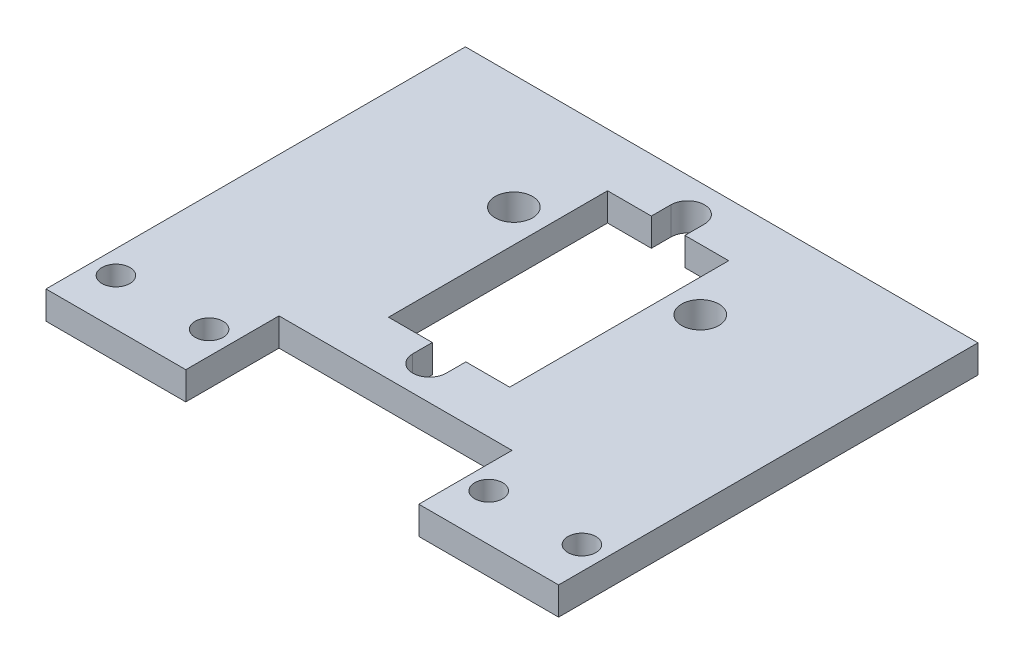
SolidWorks part; units mm, degrees
ref_plane "Front Plane" through (0, 0, 0) normal (0, 0, 1) x (1, 0, 0)
ref_plane "Top Plane" through (0, 0, 0) normal (0, 1, 0) x (1, 0, 0)
ref_plane "Right Plane" through (0, 0, 0) normal (1, 0, 0) x (0, 0, -1)
sketch "Sketch1" plane through (0, 0, 0) normal (0, 1, 0) x (1, 0, 0)
  line L0 (0, 0) -> (15, 0)
  line L1 (15, 0) -> (15, 10)
  line L2 (15, 10) -> (40, 10)
  line L3 (40, 10) -> (40, 0)
  line L4 (40, 0) -> (55, 0)
  line L5 (55, 0) -> (55, 45)
  line L6 (55, 45) -> (0, 45)
  line L7 (0, 45) -> (0, 0)
  line L8 (27.5, 10) -> (27.5, 45) construction
  line L9 (21, 39.25) -> (34, 39.25)
  line L10 (21, 39.25) -> (21, 15.75)
  line L11 (21, 15.75) -> (34, 15.75)
  line L12 (34, 39.25) -> (34, 15.75)
  line L13 (0, 27.5) -> (55, 27.5) construction
  line L14 (27.5, 5) -> (32.5, 5) construction
  line L15 (27.5, 5) -> (22.5, 5) construction
  circle A0 centre (27.5, 5) radius 1.5 construction
  circle A1 centre (32.5, 5) radius 1.5 construction
  circle A2 centre (37.5, 5) radius 1.5 construction
  circle A3 centre (42.5, 5) radius 1.5
  circle A4 centre (47.5, 5) radius 1.5 construction
  circle A5 centre (52.5, 5) radius 1.5
  circle A6 centre (22.5, 5) radius 1.5 construction
  circle A7 centre (17.5, 5) radius 1.5 construction
  circle A8 centre (12.5, 5) radius 1.5
  circle A9 centre (7.5, 5) radius 1.5 construction
  circle A10 centre (2.5, 5) radius 1.5
  circle A11 centre (27.5, 41.35) radius 1.1
  circle A13 centre (27.5, 13.65) radius 1.1
  point P13 (27.5, 39.25)
  point P14 (27.5, 45)
  point P19 (27.5, 27.5)
  point P20 (34, 27.5)
  point P50 (15, 5)
  dimension "D6" = 3
  dimension "D13" = 2.2
  dimension "D14" = 13.85
  dimension "D1" = 23.5
  dimension "D2" = 35
  dimension "D3" = 15
  dimension "D4" = 15
  dimension "D5" = 25
  dimension "D8" = 5
  dimension "D10" = 5
  dimension "D11" = 10
  dimension "D12" = 13
  dimension "D7" = 6
  dimension "D9" = 6
extrude "Boss-Extrude1" add sketch "Sketch1" along normal blind 3
sketch "Sketch2" plane through (0, 3, 0) normal (0, 1, 0) x (1, 0, 0)
  line L0 (27.5, 45) -> (27.5, 10) construction
  line L1 (55, 45) -> (0, 45) construction
  line L2 (15, 10) -> (40, 10) construction
  circle A1 centre (17.5, 32.7) radius 2 construction
  circle A2 centre (17.5, 32.7) radius 2
  circle A3 centre (37.5, 32.7) radius 2
extrude "Cut-Extrude1" cut sketch "Sketch2" against normal through all
sketch "Sketch3" plane through (0, 3, 0) normal (0, 1, 0) x (1, 0, 0)
  point P0 (27.5, 13.65)
  point P3 (27.5, 41.35)
hole_wizard "M3 Clearance Hole1" positions "Sketch3" profile "Sketch4" hole size "M3" standard "ANSI Metric" end condition through all
sketch "Sketch4" plane through (27.5, 3, -13.65) normal (1, 0, 0) x (0, 0, 1)
  line L0 (0, 0) -> (0, 3)
  line L1 (0, 3) -> (1.8, 3)
  line L2 (1.8, 3) -> (1.8, 0)
  line L5 (1.8, 0) -> (0, 0)
  line L11 (0, -6.35) -> (0, 107.95) construction
  dimension "Thru Hole Dia." = 3.6
  dimension "Thru Hole Depth" = 3
sketch "Sketch5" plane through (0, 3, 0) normal (0, 1, 0) x (1, 0, 0)
  line L0 (21, 15.75) -> (34, 15.75) construction
  line L1 (34, 39.25) -> (21, 39.25) construction
  line L2 (21, 15.75) -> (34, 15.75)
  line L3 (34, 39.25) -> (21, 39.25)
  line L4 (25.7, 13.65) -> (25.7, 15.75)
  line L5 (29.3, 13.65) -> (29.3, 15.75)
  line L6 (29.3, 41.35) -> (29.3, 39.25)
  line L7 (25.7, 41.35) -> (25.7, 39.25)
  circle A0 centre (27.5, 41.35) radius 1.8 construction
  circle A1 centre (27.5, 13.65) radius 1.8 construction
  circle A2 centre (27.5, 41.35) radius 1.8
  circle A3 centre (27.5, 13.65) radius 1.8
  circle M3 centre (27.5, 13.65) radius 1.8
  circle M4 centre (27.5, 41.35) radius 1.8
extrude "Cut-Extrude2" cut sketch "Sketch5" against normal through all contours L5 L2 L4 M3 | L7 L3 L6 M4 region at (27.5, 3, -15.7083) region at (27.5, 3, -39.2917)
